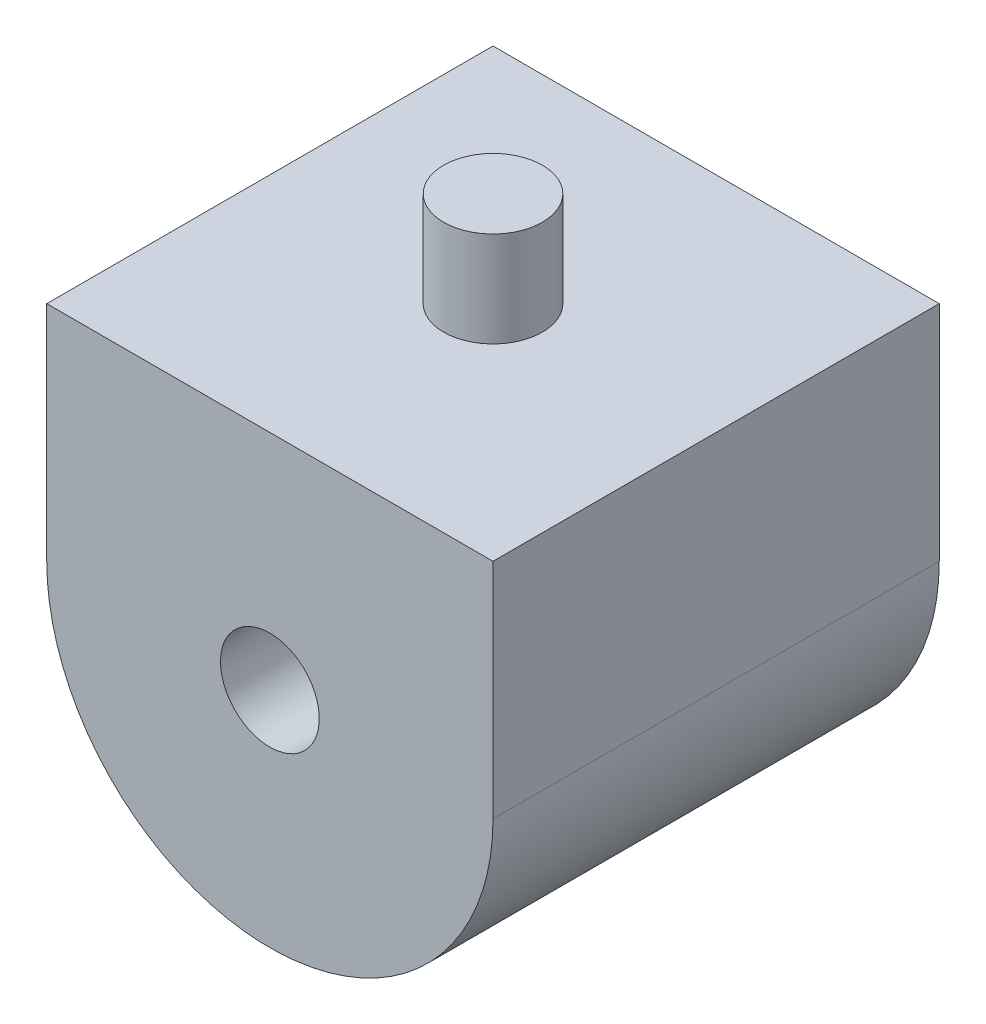
SolidWorks part; units mm, degrees
ref_plane "Front Plane" through (0, 0, 0) normal (0, 0, 1) x (1, 0, 0)
ref_plane "Top Plane" through (0, 0, 0) normal (0, 1, 0) x (1, 0, 0)
ref_plane "Right Plane" through (0, 0, 0) normal (1, 0, 0) x (0, 0, -1)
sketch "Sketch1" plane through (0, 0, 0) normal (0, 0, 1) x (1, 0, 0)
  line L2 (-19.05, -9.525) -> (-19.05, 9.525)
  line L3 (-19.05, 9.525) -> (19.05, 9.525)
  line L4 (19.05, -9.525) -> (19.05, 9.525)
  line L5 (-19.05, -9.525) -> (19.05, 9.525) construction
  line L6 (-19.05, 9.525) -> (19.05, -9.525) construction
  arc A0 (-19.05, -9.525) -> (19.05, -9.525) centre (0, -9.525) ccw
  point P0 (0, 0)
  dimension "D1" = 38.1
  dimension "D2" = 19.05
extrude "Boss-Extrude1" add sketch "Sketch1" along normal blind 38.1 contours L3 L4 A0 L2
sketch "Sketch2" plane through (0, 0, 0) normal (0, 0, -1) x (-1, 0, 0)
  circle A0 centre (0, -9.525) radius 4.2164
  dimension "D1" = 8.4328
extrude "Cut-Extrude1" cut sketch "Sketch2" against normal blind 38.1
sketch "Sketch3" plane through (0, 9.525, 0) normal (0, 1, 0) x (1, 0, 0)
  circle A0 centre (0, -19.05) radius 4.2164
  dimension "D1" = 8.4328
extrude "Boss-Extrude2" add sketch "Sketch3" along normal blind 8.128
sketch "Sketch4" plane through (0, 17.653, 0) normal (0, 1, 0) x (1, 0, 0)
  line L0 (0, -27.559) -> (0, -10.541) construction
  line L1 (-5.08, -27.559) -> (-5.08, -10.541)
  line L2 (5.08, -27.559) -> (5.08, -10.541)
  arc A0 (-5.08, -27.559) -> (5.08, -27.559) centre (0, -27.559) ccw
  arc A1 (5.08, -10.541) -> (-5.08, -10.541) centre (0, -10.541) ccw
  circle A2 centre (0, -19.05) radius 4.2164
  point P2 (0, -19.05)
  dimension "D1" = 17.018
  dimension "D2" = 10.16
extrude "Boss-Extrude3" [suppressed] add sketch "Sketch4" against normal blind 1.7145 contours A2 | L2 A1 L1 A0
